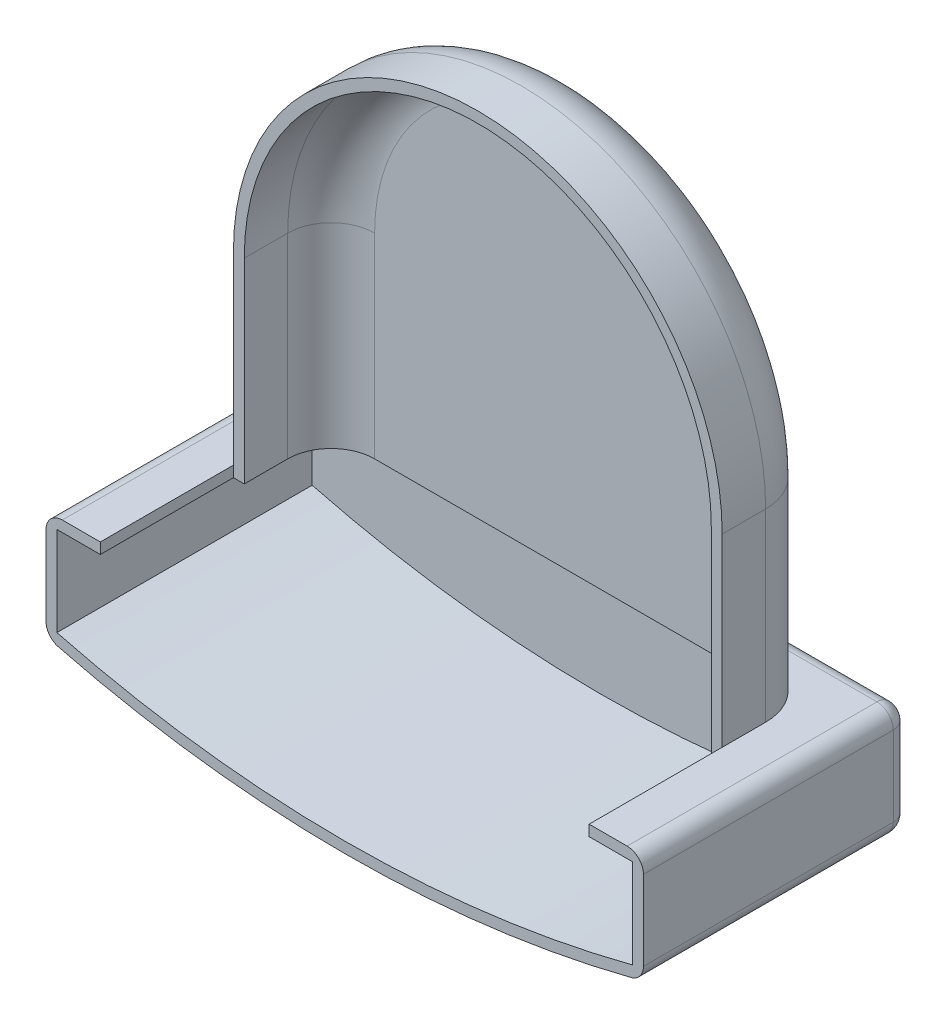
SolidWorks part; units mm, degrees
ref_plane "Front Plane" through (0, 0, 0) normal (0, 0, 1) x (1, 0, 0)
ref_plane "Top Plane" through (0, 0, 0) normal (0, 1, 0) x (1, 0, 0)
ref_plane "Right Plane" through (0, 0, 0) normal (1, 0, 0) x (0, 0, -1)
sketch "Sketch1" plane through (0, 0, 0) normal (0, 0, 1) x (1, 0, 0)
  line L0 (0, 0) -> (110, 0)
  line L1 (110, 0) -> (110, -20)
  line L2 (0, 0) -> (0, -20)
  arc A0 (0, -20) -> (110, -20) centre (55, 186.4407) ccw
  dimension "D1" = 20
  dimension "D2" = 20
  dimension "D3" = 110
extrude "Boss-Extrude1" add sketch "Sketch1" along normal blind 49
sketch "Sketch3" plane through (0, 0, 49) normal (0, 0, 1) x (1, 0, 0)
  line L3 (10, 3.9399) -> (10, -2)
  line L4 (55, 20.4208) -> (55, -2) construction
  line L5 (0, 0) -> (0, -20) construction
  line L6 (2, -2) -> (2, -18.4573)
  line L7 (108, -18.4573) -> (108, -2)
  line L8 (108, -2) -> (2, -2)
  line L9 (2, -2) -> (2, -18.4573)
  line L10 (108, -18.4573) -> (108, -2)
  line L11 (108, -2) -> (100, -2)
  line L12 (100, 3.9399) -> (100, -2)
  line L13 (110, -20) -> (110, 0) construction
  line L14 (10, -2) -> (2, -2)
  line L15 (55, -25.201) -> (55, -36.1035) construction
  line L16 (10, 3.9399) -> (100, 3.9399)
  arc A2 (2, -18.4573) -> (108, -18.4573) centre (55, 186.4407) ccw
  arc A3 (2, -18.4573) -> (108, -18.4573) centre (55, 186.4407) ccw
  dimension "D2" = 10
  dimension "D3" = 10
  dimension "D1" = 2
extrude "Cut-Extrude1" cut sketch "Sketch3" against normal offset from surface (39 mm away) 10 up to face at (55, -11.8002, 0)
shell "Shell2" thickness 2 removed face at (55, -6.4573, 10)
sketch "Sketch4" plane through (0, 0, 0) normal (0, 1, 0) x (1, 0, 0)
  line L0 (10, -24.5) -> (100, -24.5) construction
  line L3 (10, -49) -> (10, -10) construction
  line L4 (10, -24.5) -> (100, -24.5)
  line L5 (10, -24.5) -> (10, -6.5)
  line L6 (10, -6.5) -> (100, -6.5)
  line L7 (100, -24.5) -> (100, -6.5)
  dimension "D1" = 18
  dimension "D2" = 90
ref_plane "Plane1" through (0, 79, 0) normal (0, 1, 0) x (1, 0, 0)
sketch "Sketch5" plane through (0, 79, 0) normal (0, 1, 0) x (1, 0, 0)
  line L1 (100, -24.5) -> (10, -24.5)
  line L2 (100, -24.5) -> (100, -6.5)
  line L3 (100, -6.5) -> (10, -6.5)
  line L4 (10, -24.5) -> (10, -6.5)
extrude "Boss-Extrude8" add sketch "Sketch5" against normal up to surface (81 mm away)
sketch "Sketch6" plane through (0, 0, 6.5) normal (0, 0, -1) x (-1, 0, 0)
  line L0 (-55, 0) -> (-55, 79) construction
  line L1 (-110, 0) -> (0, 0) construction
  line L2 (26.95, 79) -> (-26.95, 79) construction
  line L3 (-100, 84.8929) -> (-10, 84.8929)
  line L5 (-100, 34) -> (-100, 84.8929)
  line L8 (-10, 84.8929) -> (-10, 34)
  arc A0 (-10, 34) -> (-100, 34) centre (-55, 34) ccw
  dimension "D1" = 90
extrude "Cut-Extrude2" cut sketch "Sketch6" against normal through all contours L3 L8 A0 L5
fillet "Fillet1" radius 10 3 edges at (10, 17, 6.5) (100, 17, 6.5) (55, 79, 6.5)
shell "Shell4" thickness 2 removed face at (55, 18.1667, 24.5)
sketch "Sketch11" plane through (0, 0, 24.5) normal (0, 0, 1) x (1, 0, 0)
  line L0 (108, -2) -> (2, -2) construction
  line L1 (12, 0) -> (97.9757, 0)
  line L2 (12, 0) -> (12, -2)
  line L3 (12, -2) -> (97.9757, -2)
  line L4 (97.9757, 0) -> (97.9757, -2)
sketch "Sketch12" plane through (0, 0, 0) normal (0, 1, 0) x (1, 0, 0)
  line L4 (90, -8.5) -> (20, -8.5)
  line L5 (12, -16.5) -> (12, -24.5)
  line L6 (12, -24.5) -> (98, -24.5)
  line L7 (98, -24.5) -> (98, -16.5)
  line L8 (90, -8.5) -> (20, -8.5)
  line L9 (12, -16.5) -> (12, -24.5)
  line L10 (12, -24.5) -> (98, -24.5)
  line L11 (98, -24.5) -> (98, -16.5)
  arc A2 (20, -8.5) -> (12, -16.5) centre (20, -16.5) ccw
  arc A3 (98, -16.5) -> (90, -8.5) centre (90, -16.5) ccw
  arc A4 (20, -8.5) -> (12, -16.5) centre (20, -16.5) ccw
  arc A5 (98, -16.5) -> (90, -8.5) centre (90, -16.5) ccw
  dimension "D1" = 0
extrude "Cut-Extrude6" cut sketch "Sketch12" against normal blind 3
sketch "Sketch9" plane through (0, 0, 6.5) normal (0, 0, -1) x (-1, 0, 0)
  line L6 (-90, 0) -> (-20, 0)
  line L7 (-20, 0) -> (-20, 34)
  line L8 (-90, 34) -> (-90, 0)
  line L9 (-90, 0) -> (-20, 0)
  line L10 (-20, 0) -> (-20, 34)
  line L11 (-90, 34) -> (-90, 0)
  arc A2 (-20, 34) -> (-90, 34) centre (-55, 34) ccw
  arc A3 (-20, 34) -> (-90, 34) centre (-55, 34) ccw
  dimension "D1" = 0
extrude "Boss-Extrude9" add sketch "Sketch9" along normal blind 2
sketch "Sketch10" plane through (0, 0, 4.5) normal (0, 0, -1) x (-1, 0, 0)
  circle A0 centre (-55, 34) radius 30
  dimension "D1" = 60
extrude "Cut-Extrude4" cut sketch "Sketch10" against normal blind 1
fillet "Fillet2" radius 2 3 edges at (20, 17, 4.5) (55, 69, 4.5) (90, 17, 4.5)
fillet "Fillet3" radius 3 8 edges at (0, -20, 24.5) (110, -20, 24.5) (0, -10, 0) (55, -27.201, 0) (55, 0, 0) (110, 0, 24.5) (0, 0, 24.5) (110, -10, 0)
